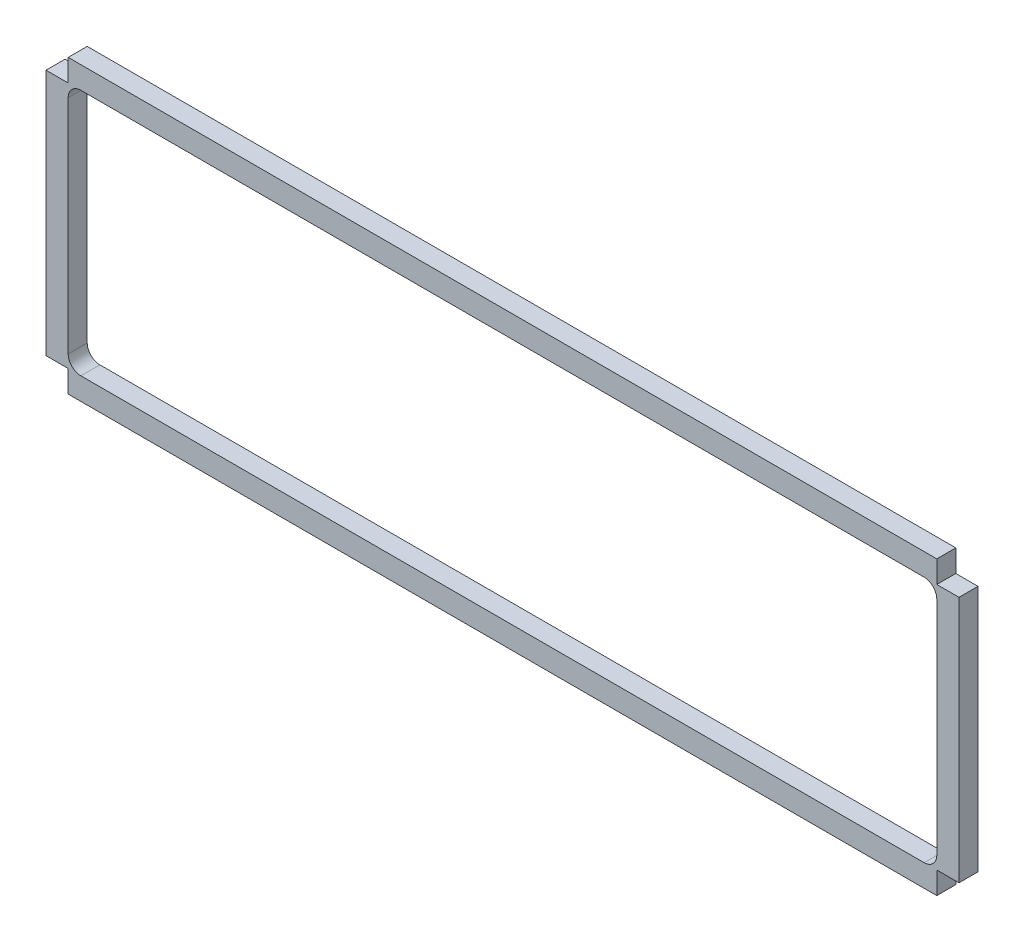
SolidWorks part; units mm, degrees
material "ABS PC"
ref_plane "Front Plane" through (0, 0, 0) normal (0, 0, 1) x (1, 0, 0)
ref_plane "Top Plane" through (0, 0, 0) normal (0, 1, 0) x (1, 0, 0)
ref_plane "Right Plane" through (0, 0, 0) normal (1, 0, 0) x (0, 0, -1)
sketch "Sketch1" plane through (0, 0, 0) normal (0, 0, 1) x (1, 0, 0)
  line L0 (0, 0) -> (0, 46) construction
  line L1 (68.5, 46) -> (-68.5, 46)
  line L2 (-68.5, 46) -> (-68.5, 42.5)
  line L3 (-68.5, 42.5) -> (-72, 42.5)
  line L4 (-72, 42.5) -> (-72, 3.5)
  line L5 (-72, 3.5) -> (-68.5, 3.5)
  line L6 (-68.5, 3.5) -> (-68.5, 0)
  line L7 (-68.5, 0) -> (68.5, 0)
  line L8 (68.5, 3.5) -> (68.5, 0)
  line L9 (72, 3.5) -> (68.5, 3.5)
  line L10 (68.5, 46) -> (68.5, 42.5)
  line L11 (68.5, 42.5) -> (72, 42.5)
  line L12 (72, 42.5) -> (72, 3.5)
  dimension "D1" = 72
  dimension "D2" = 3.5
  dimension "D3" = 46
extrude "Boss-Extrude1" add sketch "Sketch1" along normal blind 3
sketch "Sketch2" plane through (0, 0, 3) normal (0, 0, 1) x (1, 0, 0)
  line L0 (68.5, 5.5) -> (68.5, 40.5) construction
  line L1 (-66.5, 3.5) -> (66.5, 3.5) construction
  line L2 (-68.5, 40.5) -> (-68.5, 5.5) construction
  line L3 (66.5, 42.5) -> (-66.5, 42.5) construction
  line L4 (68.5, 5.5) -> (68.5, 40.5)
  line L5 (-66.5, 3.5) -> (66.5, 3.5)
  line L6 (-68.5, 40.5) -> (-68.5, 5.5)
  line L7 (66.5, 42.5) -> (-66.5, 42.5)
  arc A0 (66.5, 3.5) -> (68.5, 5.5) centre (66.5, 5.5) ccw construction
  arc A1 (68.5, 40.5) -> (66.5, 42.5) centre (66.5, 40.5) ccw construction
  arc A2 (-68.5, 5.5) -> (-66.5, 3.5) centre (-66.5, 5.5) ccw construction
  arc A3 (-66.5, 42.5) -> (-68.5, 40.5) centre (-66.5, 40.5) ccw construction
  arc A4 (66.5, 3.5) -> (68.5, 5.5) centre (66.5, 5.5) ccw
  arc A5 (68.5, 40.5) -> (66.5, 42.5) centre (66.5, 40.5) ccw
  arc A6 (-68.5, 5.5) -> (-66.5, 3.5) centre (-66.5, 5.5) ccw
  arc A7 (-66.5, 42.5) -> (-68.5, 40.5) centre (-66.5, 40.5) ccw
extrude "Cut-Extrude3" cut sketch "Sketch2" against normal up to surface (3 mm away) contours A4 L4 A5 L7 A7 L6 A6 L5 up to face at (0, 23, 0)
